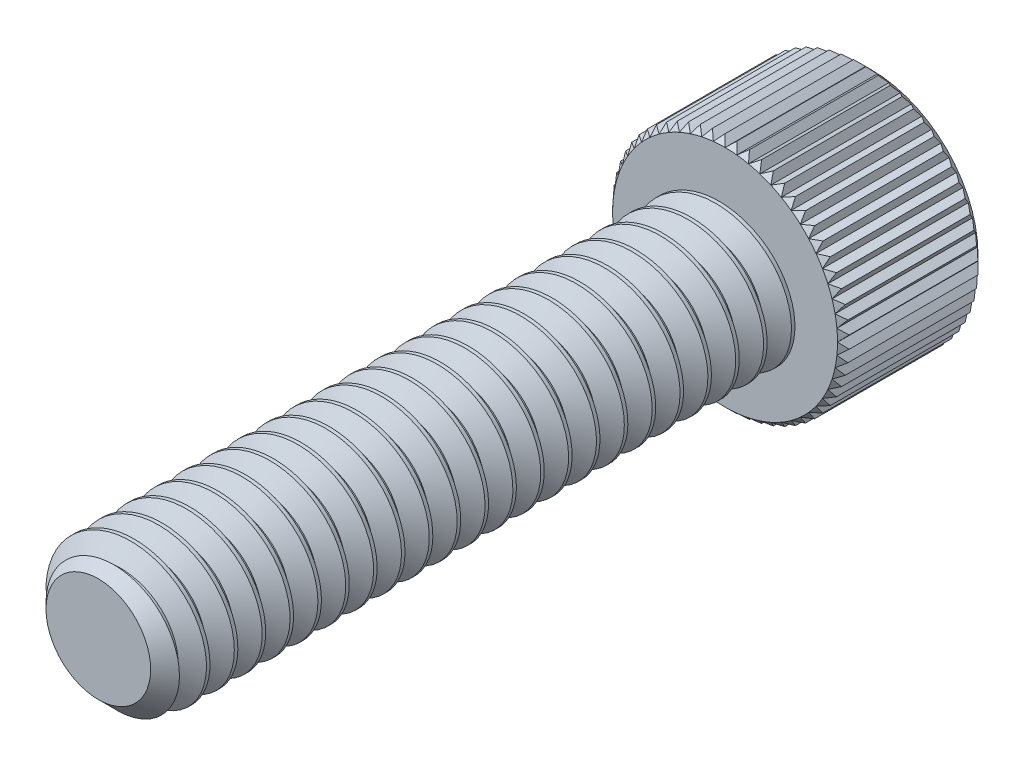
SolidWorks part; units mm, degrees
note: '?' marks a value the reader was unsure of.
ref_plane "Front Plane" through (0, 0, 0) normal (0, 0, 1) x (1, 0, 0)
ref_plane "Top Plane" through (0, 0, 0) normal (0, 1, 0) x (1, 0, 0)
ref_plane "Right Plane" through (0, 0, 0) normal (1, 0, 0) x (0, 0, -1)
sketch "Sketch0" plane through (0, 0, 0) normal (1, 0, 0) x (0, 0, -1)
  line L0 (0, 0) -> (7.9375, 0) construction
  point P2 (9.7917, 0)
  point P4 (0.254, 0)
  dimension "D1" = 7.9375
  dimension "D2" = 1.8542
  dimension "Min Thread" = 0.254
sketch "Sketch1" plane through (0, 0, 0) normal (0, 0, 1) x (1, 0, 0)
  circle A0 centre (0, 0) radius 0.9271
  dimension "OD" = 1.8542
extrude "Extrude1" add sketch "Sketch1" against normal blind 7.9375
sketch "Sketch2" plane through (0, 0, 0) normal (0, 0, 1) x (1, 0, 0)
  circle A0 centre (0, 0) radius 0.9271 construction
  circle A1 centre (0, 0) radius 0.9271
curve "Helix/Spiral1" pitch 0.3528 height 8.2903 turns 23.5 parameters "pitch"=0.3528
chamfer "Chamfer3" distance 0.2646 angle 45 1 edges at (0.9271, 0, 0)
sketch "Sketch3" plane through (0, 0, 0) normal (1, 0, 0) x (0, 0, -1)
  line L0 (-0.3087, 0.9271) -> (-0.1764, 0.698)
  line L1 (-0.1764, 0.698) -> (-0.1323, 0.698)
  line L2 (-0.1323, 0.698) -> (0, 0.9271)
  line L3 (-0.3087, 0.9271) -> (0, 0.9271)
  line L4 (-0.1543, 0.9271) -> (-0.1543, 0.698) construction
  line L5 (-0.2425, 0.8125) -> (-0.0661, 0.8125) construction
  line L6 (0, 0.9271) -> (0, -0.9271) construction
  dimension "D1" = 0.0441
  dimension "D2" = 0.1764
  dimension "D3" = 60
sweep "Cut-Sweep1" cut profiles "Sketch3" path "Helix/Spiral1" align with end faces yes
sketch "Sketch5" plane through (0, 0, 0) normal (1, 0, 0) x (0, 0, -1)
  line L0 (7.9375, -0.6615) -> (7.9375, 0.7038) construction
  line L1 (7.9375, 0.9271) -> (0.254, 0.9271)
  line L2 (7.9375, 0.9271) -> (7.9375, 0)
  line L3 (7.9375, 0) -> (-0.0834, 0)
  line L4 (0, 0) -> (7.9375, 0) construction
  line L5 (0.254, 0.9271) -> (-0.0834, 0)
  line L6 (0, 0) -> (10.4775, 0) construction
  dimension "D1" = 70
  dimension "D3" = 2.54
revolve "partially thread" [suppressed] add sketch "Sketch5" angle 360 about L6
sketch "Sketch6" plane through (0, 0, -7.9375) normal (0, 0, -1) x (-1, 0, 0)
  circle A0 centre (0, 0) radius 1.4986
  dimension "head dia" = 2.9972
extrude "Extrude2" add sketch "Sketch6" along normal blind 1.8542
sketch "Sketch7" plane through (0, 0, -9.7917) normal (0, 0, -1) x (-1, 0, 0)
  line L1 (0, 0.9165) -> (-0.7937, 0.4583)
  line L2 (-0.7937, 0.4583) -> (-0.7937, -0.4583)
  line L3 (-0.7937, -0.4583) -> (0, -0.9165)
  line L4 (0, -0.9165) -> (0.7938, -0.4583)
  line L5 (0.7938, -0.4583) -> (0.7937, 0.4583)
  line L6 (0.7937, 0.4583) -> (0, 0.9165)
  circle A0 centre (0, 0) radius 0.7937 construction
  dimension "hex dia" = 1.5875
extrude "Cut-Extrude1" cut sketch "Sketch7" against normal blind 1.1906
sketch "Sketch8" plane through (0, 0, -9.7917) normal (0, 0, -1) x (-1, 0, 0)
  circle A0 centre (0, 0) radius 0.9165
extrude "Cut-Extrude2" cut sketch "Sketch8" against normal through all draft 45
chamfer "Chamfer1" distance 0.1499 angle 45 1 edges at (-1.4986, 0, -9.7917)
chamfer "Chamfer2" distance 0.0749 angle 45 1 edges at (-1.4986, 0, -7.9375)
sketch "Sketch9" plane through (0, 0, 0) normal (1, 0, 0) x (0, 0, -1)
  line L0 (0, 0.9271) -> (0, -0.9271) construction
  line L1 (0.8819, 0.9271) -> (0.8819, -0.9271) construction
  line L2 (9.7917, 1.4986) -> (9.7917, -1.4986) construction
  line L3 (7.9375, 1.4986) -> (7.9375, -1.4986) construction
  line L4 (7.9375, 1.4237) -> (7.9375, -1.4237) construction
  line L5 (9.7917, -1.3487) -> (9.7917, 1.3487) construction
  line L6 (7.9375, -1.4986) -> (7.9375, 1.4986) construction
  line L7 (0, 0.6625) -> (0, -0.6625) construction
  line L8 (-0.3087, 0.9271) -> (0, 0.9271) construction
  line L9 (0.8819, 0) -> (0, 0) construction
  dimension "D1" = 0.8819
sketch "Sketch10" plane through (0, 0, -7.9375) normal (0, 0, 1) x (1, 0, 0)
  line L0 (-0.1613, 1.5735) -> (0, 1.4237)
  line L1 (0, 1.4237) -> (0.1613, 1.5735)
  line L2 (0, 1.4237) -> (0, 1.5735) construction
  line L3 (-0.1613, 1.5735) -> (0.1613, 1.5735)
  line L4 (0, -1.9618) -> (0, 1.9618) construction
  line L5 (0, 0) -> (0.0784, 1.4965) construction
  line L6 (-0.0784, 1.4965) -> (0, 0) construction
  circle A2 centre (0, 0) radius 1.4986 construction
  circle A5 centre (0, 0) radius 1.4237 construction
  dimension "D1" = 6
  dimension "D2" = 0.1499
extrude "Cut-Extrude3" cut sketch "Sketch10" against normal through all
pattern_circular "CirPattern1" count 60 over 360 about axis through (0, 0, 0) along (0, 0, 1) of "Cut-Extrude3"
ref_plane "Contact Plane 1" through (0, 0, -7.9375) normal (0, 0, 1) x (1, 0, 0)
ref_axis "Center Axis 1" through (0, 0, 0.8878) along (0, 0, -1)?
equation "\"D3@Helix/Spiral1\" = \"screw length@Extrude1\"+\"pitch@Helix/Spiral1\""
equation "\"D1@Sketch3\" = \"pitch@Helix/Spiral1\"*.125"
equation "\"D2@Sketch3\" = \"pitch@Helix/Spiral1\"*.5"
equation "\"D1@Cut-Extrude1\" = \"hex dia@Sketch7\"*.75"
equation "\"D1@Chamfer1\" = \"head dia@Sketch6\"*.05"
equation "\"D1@Sketch9\" = \"pitch@Helix/Spiral1\"*2.50"
equation "\"D1@Chamfer2\" = \"D1@Chamfer1\"/2"
equation "\"D1@Chamfer3\" = \"pitch@Helix/Spiral1\"*.750"
equation "\"D1@Sketch0\" = \"screw length@Extrude1\""
equation "\"D2@Sketch0\" = \"head depth@Extrude2\""
equation "\"D2@Sketch10\"=\"D1@Chamfer1\""
equation "\"D1@CirPattern1\"=\"D3@CirPattern1\"/\"D1@Sketch10\""
